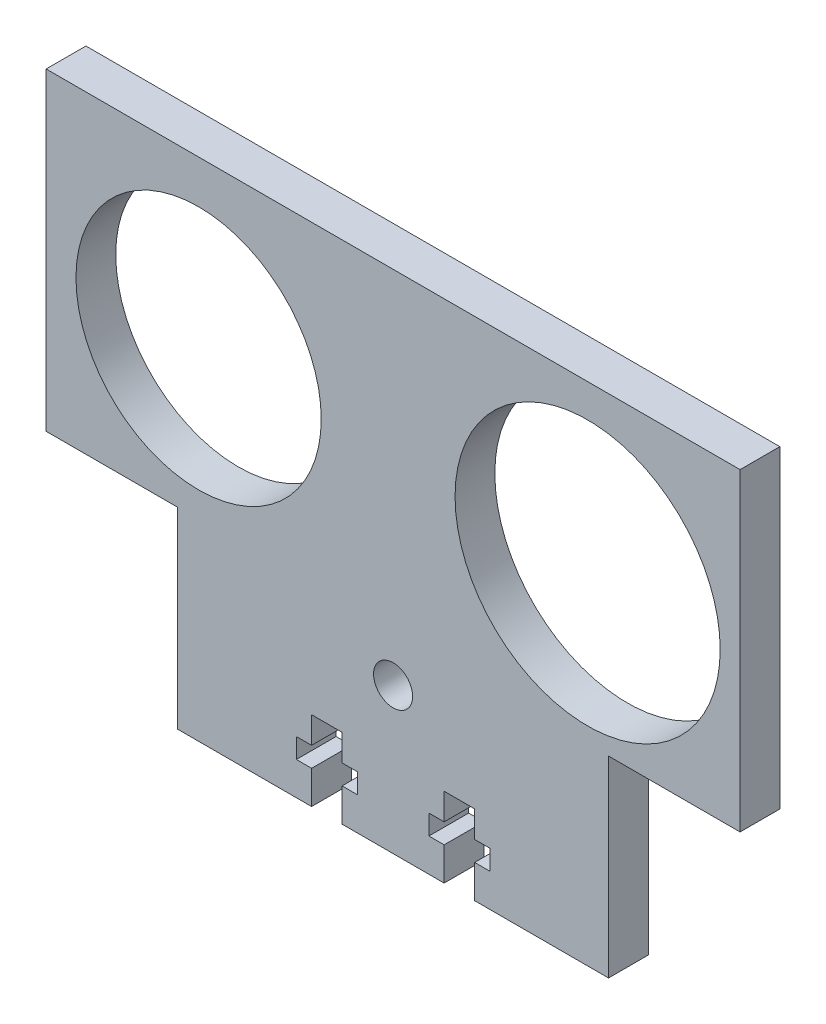
SolidWorks part; units mm, degrees
material "ABS"
ref_plane "Front Plane" through (0, 0, 0) normal (0, 0, 1) x (1, 0, 0)
ref_plane "Top Plane" through (0, 0, 0) normal (0, 1, 0) x (1, 0, 0)
ref_plane "Right Plane" through (0, 0, 0) normal (1, 0, 0) x (0, 0, -1)
sketch "Sketch1" plane through (0, 0, 0) normal (0, 0, 1) x (1, 0, 0)
  line L0 (0, 0) -> (-29.3449, 29.3449) construction
  line L1 (0, 0) -> (0, 54.3449) construction
  line L2 (-32.5, 7) -> (-32.5, -22)
  line L3 (-32.5, -22) -> (32.5, -22)
  line L4 (32.5, -22) -> (32.5, 7)
  line L5 (0, 0) -> (0, -22) construction
  line L6 (0, 0) -> (29.3449, 29.3449) construction
  line L10 (-32.5, 7) -> (-52.3449, 7)
  line L11 (-52.3449, 7) -> (-52.3449, 54.3449)
  line L12 (-52.3449, 54.3449) -> (52.3449, 54.3449)
  line L13 (52.3449, 54.3449) -> (52.3449, 7)
  line L14 (52.3449, 7) -> (32.5, 7)
  circle A0 centre (0, 0) radius 2.95
  circle A1 centre (29.3449, 29.3449) radius 20
  circle A2 centre (-29.3449, 29.3449) radius 18.5
  dimension "D1" = 5.9
  dimension "D9" = 37
  dimension "D11" = 40
  dimension "D2" = 41.5
  dimension "D4" = 45
  dimension "D5" = 22
  dimension "D6" = 65
  dimension "D3" = 23
  dimension "D7" = 25
  dimension "D8" = 29
  dimension "D10" = 45
extrude "Boss-Extrude1" add sketch "Sketch1" along normal blind 6
sketch "Sketch3" plane through (0, 0, 6) normal (0, 0, 1) x (1, 0, 0)
  line L0 (-32.5, -22) -> (32.5, -22) construction
  line L1 (-12.3, -22) -> (-7.7, -22)
  line L2 (-12.3, -22) -> (-12.3, -17)
  line L3 (-12.3, -10) -> (-7.7, -10)
  line L4 (-7.7, -22) -> (-7.7, -17)
  line L5 (0, 0) -> (0, -22) construction
  line L6 (-7.7, -14) -> (-5.4, -14)
  line L7 (-14.6, -14) -> (-12.3, -14)
  line L8 (-14.6, -14) -> (-14.6, -17)
  line L9 (-14.6, -17) -> (-12.3, -17)
  line L10 (-5.4, -14) -> (-5.4, -17)
  line L11 (-12.3, -14) -> (-12.3, -10)
  line L12 (-7.7, -17) -> (-5.4, -17)
  line L13 (-7.7, -14) -> (-7.7, -10)
  line L14 (7.7, -14) -> (7.7, -10)
  line L15 (7.7, -17) -> (5.4, -17)
  line L16 (12.3, -14) -> (12.3, -10)
  line L17 (5.4, -14) -> (5.4, -17)
  line L18 (14.6, -17) -> (12.3, -17)
  line L19 (14.6, -14) -> (14.6, -17)
  line L20 (14.6, -14) -> (12.3, -14)
  line L21 (7.7, -14) -> (5.4, -14)
  line L22 (7.7, -22) -> (7.7, -17)
  line L23 (12.3, -10) -> (7.7, -10)
  line L24 (12.3, -22) -> (12.3, -17)
  line L25 (12.3, -22) -> (7.7, -22)
  point P6 (-10, -10)
  point P18 (-13.45, -17)
  dimension "D1" = 4.6
  dimension "D2" = 10
  dimension "D3" = 12
  dimension "D4" = 9.2
  dimension "D5" = 3
  dimension "D6" = 5
extrude "Cut-Extrude2" cut sketch "Sketch3" against normal through all
equation "\"smallPulleyTeeth\"= 15"
equation "\"largePulleyTeeth\"= 30"
equation "\"eighthThick\"= 2.9mm"
equation "\"sixteenthThick\" = 1.7mm"
equation "\"quarterThick\"=6.0mm"
equation "\"OD\" = 146mm"
equation "\"puckAngle\" = 60.5deg"
equation "\"puckDiam\" = 76.5mm"
equation "\"axlePress\" = 5.9mm"
equation "\"D1@Sketch1\"=\"axlePress\""
equation "\"D1@Boss-Extrude1\"=\"quarterThick\""
equation "\"press\" = 0.2mm"
equation "\"wheelClear\" = 0.3mm"
equation "\"10-32clear\" = 4.8mm"
equation "\"D1@Sketch3\"=\"10-32clear\"-\"press\""
equation "\"6-32clear\" = 3.3mm"
equation "\"8-32clear\" = 4.0mm"
equation "\"wheelHeight\" = 22mm"
equation "\"D5@Sketch1\"=\"wheelHeight\""
equation "\"D8@Sketch1\"=\"eighthThick\"*10"
equation "\"4-40clear\" = 3.0mm"
equation "\"wheelWell\" = 65mm"
equation "\"D6@Sketch1\"=\"wheelWell\""
